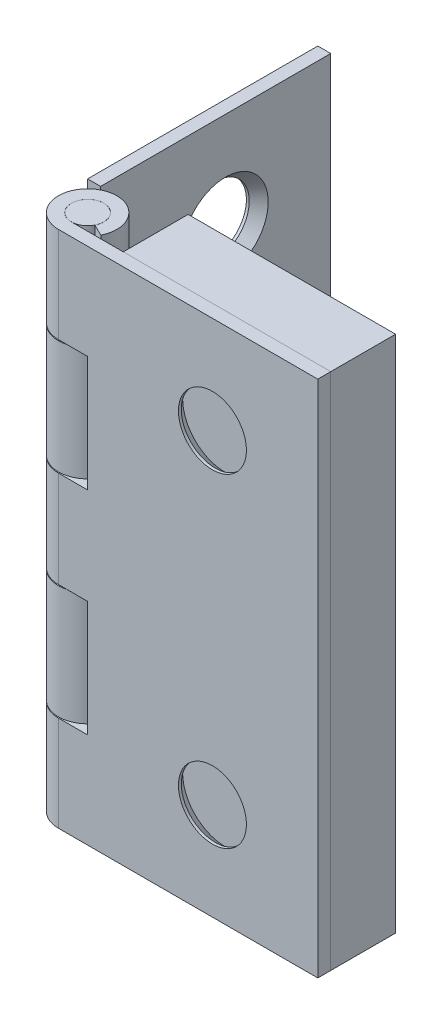
SolidWorks part; units mm, degrees
note: '?' marks a value the reader was unsure of.
ref_plane "Front" through (0, 0, 0) normal (0, 0, 1) x (1, 0, 0)
ref_plane "Top" through (0, 0, 0) normal (0, 1, 0) x (1, 0, 0)
ref_plane "Right" through (0, 0, 0) normal (1, 0, 0) x (0, 0, -1)
sketch "Sketch1" plane through (0, 0, 0) normal (0, 1, 0) x (1, 0, 0)
  line L0 (0, -0.7937) -> (12.7, -0.7937)
  line L1 (12.7, -0.7937) -> (12.7, -1.4287)
  line L2 (12.7, -1.4287) -> (0, -1.4288)
  line L3 (1.2799, -0.635) -> (0.711, -0.3528)
  line L4 (0.711, -0.3528) -> (0, 0) construction
  line L5 (1.2799, -0.635) -> (1.2011, -0.7937) construction
  arc A0 (0.711, -0.3528) -> (0, -0.7937) centre (0, 0) ccw
  arc A1 (1.2799, -0.635) -> (0, -1.4288) centre (0, 0) ccw
  dimension "B Half Width" = 12.7
  dimension "D1" = 0.1588
extrude "Extrude1" add sketch "Sketch1" along normal mid plane 25.4
ref_plane "Plane2" through (7.5406, 0, 0) normal (1, 0, 0) x (0, 0, -1)
sketch "Sketch7" plane through (7.5406, 0, 0) normal (1, 0, 0) x (0, 0, -1)
  line L0 (1.8223, 7.9375) -> (-3.6624, 7.9375) construction
  line L1 (-0.7937, 7.9375) -> (-0.7937, 10.033)
  line L2 (-0.7937, 10.033) -> (-1.2905, 9.6012)
  line L3 (-1.2905, 9.6012) -> (-1.4287, 9.6012)
  line L4 (-1.4287, 9.6012) -> (-1.4287, 7.9375)
  line L5 (-1.4287, 7.9375) -> (-0.7937, 7.9375)
  line L6 (-0.7937, 5.842) -> (-1.2905, 6.2738) construction
  line L7 (-0.7937, 12.7) -> (-0.7937, -12.7) construction
  line L9 (-1.4287, 12.7) -> (-0.7937, 12.7) construction
  line L10 (-1.4287, 12.7) -> (-1.4287, -12.7) construction
  dimension "D1" = 82
  dimension "Screw Head Dia" = 4.191
  dimension "X Thru Dia" = 3.3274
  dimension "G" = 4.7625
revolve "Cut-Revolve1" cut sketch "Sketch7" angle 360 about L0
pattern_linear "LPattern2" count 2 spacing 15.875 along (0, -1, 0) of "Cut-Revolve1"
ref_axis "Axis1" through (0, 13.97, 0) along (0, -1, 0)?
sketch "Sketch8" plane through (0, 0, 0) normal (0, 1, 0) x (1, 0, 0)
  line L0 (0, 0) -> (0, 4.3133)
  line L1 (0, 4.3133) -> (4.3133, 4.3133)
  line L2 (4.3133, 4.3133) -> (0, 0)
  dimension "D1" = 45
ref_plane "Plane3" through (0, 0, 0) normal (0.7071, 0, 0.7071) x (0.7071, 0, -0.7071)
mirror "Mirror2" about plane through (0, 0, 0) normal (0.7071, 0, 0.7071) of bodies 114 108
sketch "Sketch4" plane through (0, 0, 0) normal (0, 0, 1) x (1, 0, 0)
  line L0 (-1.4288, 12.7) -> (-1.4288, 8.0264) construction
  line L1 (-1.4288, 8.0264) -> (1.4288, 8.0264)
  line L2 (1.4288, 8.0264) -> (1.4288, 2.3622)
  line L3 (1.4288, 2.3622) -> (-1.4288, 2.3622)
  line L4 (-1.4288, 2.3622) -> (-1.4288, -2.3622) construction
  line L5 (-1.4288, -2.3622) -> (1.4288, -2.3622)
  line L6 (1.4288, -2.3622) -> (1.4288, -8.0264)
  line L7 (1.4288, -8.0264) -> (-1.4288, -8.0264)
  line L8 (-1.4288, -8.0264) -> (-1.4288, -12.7) construction
  line L9 (12.7, -12.7) -> (0, -12.7) construction
  line L10 (12.7, 12.7) -> (0, 12.7) construction
  line L11 (-1.4288, 12.7) -> (-1.4288, -12.7) construction
  line L12 (1.4288, -12.7) -> (1.4288, 12.7) construction
  line L13 (-1.4288, -8.0264) -> (-1.4288, -2.3622)
  line L14 (-1.4288, 2.3622) -> (-1.4288, 8.0264)
  dimension "D" = 4.7244
  dimension "C" = 16.0528
extrude "Cut-Extrude1" cut sketch "Sketch4" against normal through all and the other way through all
sketch "Sketch5" plane through (0, 0, 0) normal (0, 0, 1) x (1, 0, 0)
  line L0 (1.4288, -2.3622) -> (1.4288, -8.0264) construction
  line L1 (-1.4288, -12.7) -> (1.4288, -12.7)
  line L2 (-1.4288, -12.7) -> (-1.4288, -7.9756)
  line L3 (-1.4288, -7.9756) -> (1.4288, -7.9756)
  line L4 (1.4288, -12.7) -> (1.4288, -7.9756)
  line L5 (-1.4288, -8.0264) -> (-1.4288, -2.3622) construction
  line L6 (-1.4288, -2.413) -> (1.4288, -2.413)
  line L7 (-1.4288, -2.413) -> (-1.4288, 2.413)
  line L8 (-1.4288, 2.413) -> (1.4288, 2.413)
  line L9 (1.4288, -2.413) -> (1.4288, 2.413)
  line L10 (1.4288, 8.0264) -> (1.4288, 2.3622) construction
  line L11 (-1.4288, 8.0264) -> (1.4288, 8.0264) construction
  line L12 (-1.4288, 12.7) -> (1.4288, 12.7)
  line L13 (-1.4288, 12.7) -> (-1.4288, 7.9756)
  line L14 (-1.4288, 7.9756) -> (1.4288, 7.9756)
  line L15 (1.4288, 12.7) -> (1.4288, 7.9756)
  line L16 (1.4288, 2.3622) -> (-1.4288, 2.3622) construction
  line L17 (-1.4288, -2.3622) -> (1.4288, -2.3622) construction
  line L18 (1.4288, -8.0264) -> (-1.4288, -8.0264) construction
  dimension "D1" = 0.0508
  dimension "D2" = 0.0508
  dimension "D3" = 0.0508
  dimension "D4" = 0.0508
extrude "Cut-Extrude2" cut sketch "Sketch5" against normal blind 1.4287 and the other way blind 1.4287
sketch "Sketch6" plane through (0, 0, 0) normal (0, 1, 0) x (1, 0, 0)
  line L0 (0, 0) -> (0, 0.7912) construction
  line L1 (0, 0.7912) -> (0, 0.7937) construction
  circle A0 centre (0, 0) radius 0.7912
  arc A1 (0.711, -0.3528) -> (0, -0.7937) centre (0, 0) ccw construction
  dimension "D1" = 0.0025
extrude "Extrude2" add sketch "Sketch6" against normal up to surface and the other way up to surface
sketch "Sketch9" plane through (0, 0, 0.7937) normal (0, 0, -1) x (-1, 0, 0)
  line L0 (-12.7, 12.7) -> (0, 12.7) construction
  line L1 (-12.7, -12.7) -> (-2.54, -12.7)
  line L2 (-12.7, -12.7) -> (-12.7, 12.7)
  line L3 (-12.7, 12.7) -> (-2.54, 12.7)
  line L4 (-2.54, -12.7) -> (-2.54, 12.7)
  dimension "D1" = 10.16
extrude "Boss-Extrude1" add sketch "Sketch9" along normal blind 3.175 separate body
equation "\"D1@Sketch1\"=\"M Mat'l Thickness@Sketch1\"/4"
